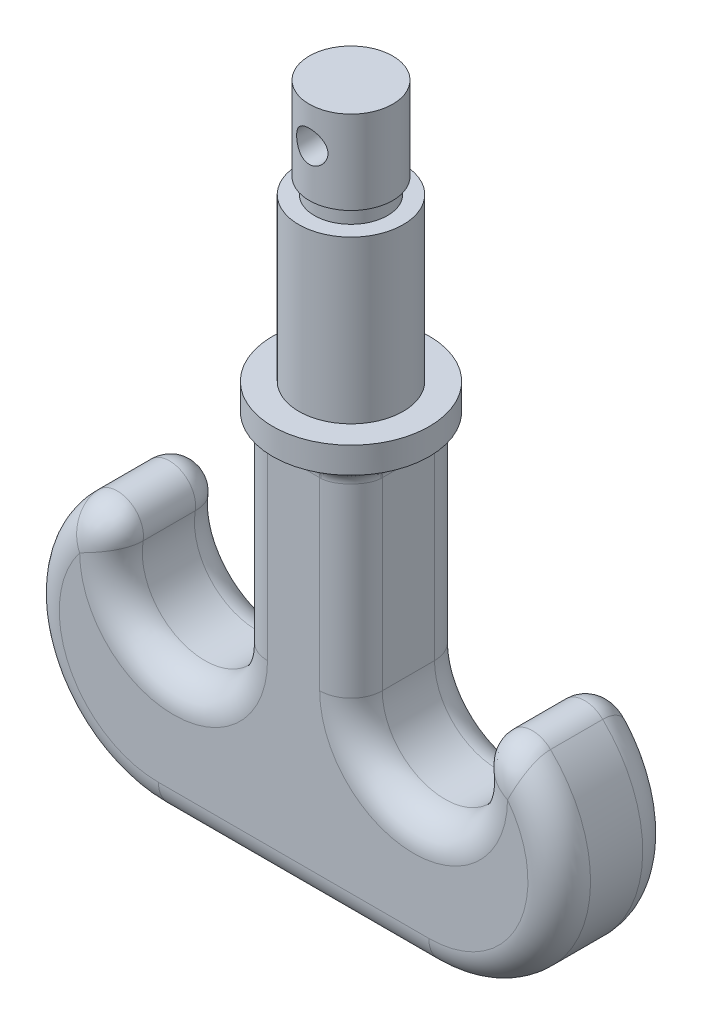
SolidWorks part; units mm, degrees
ref_plane "Front Plane" through (0, 0, 0) normal (0, 0, 1) x (1, 0, 0)
ref_plane "Top Plane" through (0, 0, 0) normal (0, 1, 0) x (1, 0, 0)
ref_plane "Right Plane" through (0, 0, 0) normal (1, 0, 0) x (0, 0, -1)
sketch "Sketch1" plane through (0, 0, 0) normal (0, 0, 1) x (1, 0, 0)
  line L0 (0, 125.5092) -> (0, 0) construction
  line L1 (0, 0) -> (0, 75)
  line L2 (11, 75) -> (-11, 75)
  line L3 (-11, 75) -> (-11, 36.6426)
  line L4 (-25.907, 0) -> (25.907, 0)
  line L5 (11, 75) -> (11, 36.6426)
  arc A0 (-11, 36.6426) -> (-34.8396, 38.5983) centre (-23, 36.6426) cw
  arc A1 (-34.8396, 38.5983) -> (-43.2391, 43.0165) centre (-39.7727, 39.4132) ccw
  arc A2 (-43.2391, 43.0165) -> (-25.907, 0) centre (-25.907, 25) ccw
  arc A3 (43.2391, 43.0165) -> (25.907, 0) centre (25.907, 25) cw
  arc A4 (34.8396, 38.5983) -> (43.2391, 43.0165) centre (39.7727, 39.4132) cw
  arc A5 (11, 36.6426) -> (34.8396, 38.5983) centre (23, 36.6426) ccw
  point P22 (49.0955, 15.6569)
  dimension "D1" = 75
  dimension "D3" = 12
  dimension "D4" = 5
  dimension "D5" = 25
  dimension "D2" = 11
extrude "Boss-Extrude2" add sketch "Sketch1" along normal mid plane 22 contours A1 A2 L4 L1 L2 L3 A0 | A5 L5 L2 L1 L4 A3 A4 region at (-12.9535, 0.9065, 0) region at (0.9065, 37.5, 0)
ref_plane "Plane1" through (0, 0, 0) normal (0, 0, 1) x (1, 0, 0)
sketch "Sketch4" plane through (0, 0, 0) normal (0, 0, 1) x (1, 0, 0)
  line L0 (0, 0) -> (0, 168.7307) construction
  line L1 (-25.907, 0) -> (25.907, 0) construction
  line L2 (0, 75) -> (15, 75)
  line L3 (11, 75) -> (-11, 75) construction
  line L4 (15, 75) -> (15, 80)
  line L5 (15, 80) -> (10, 80)
  line L6 (10, 80) -> (10, 111)
  line L7 (10, 111) -> (7, 111)
  line L8 (7, 111) -> (7, 114)
  line L9 (7, 114) -> (8, 114)
  line L10 (8, 114) -> (8, 130)
  line L11 (8, 130) -> (0, 130)
  line L12 (0, 75) -> (0, 130)
  dimension "D1" = 15
  dimension "D2" = 5
  dimension "D3" = 10
  dimension "D4" = 7
  dimension "D5" = 8
  dimension "D6" = 31
  dimension "D7" = 3
  dimension "D8" = 16
revolve "Revolve1" add sketch "Sketch4" angle 360 about L0
cosmetic thread "Cosmetic Thread1" parameters "D2"=13.797
sketch "Sketch5" plane through (0, 0, 0) normal (0, 0, 1) x (1, 0, 0)
  line L0 (8, 130) -> (-8, 130) construction
  circle A0 centre (0, 123) radius 3
  dimension "D1" = 6
  dimension "D2" = 7
extrude "Cut-Extrude1" cut sketch "Sketch5" against normal through all and the other way through all
fillet "Fillet1" radius 6 18 edges at (-11, 55.8213, -11) (-23.9812, 24.6828, -11) (-37.4451, 43.8384, -11) (-49.0955, 15.6569, -11) (0, 0, -11) (49.0955, 15.6569, -11) (37.4451, 43.8384, -11) (23.9812, 24.6828, -11) (-11, 55.8213, 11) (11, 55.8213, 11) (23.9812, 24.6828, 11) (37.4451, 43.8384, 11) (49.0955, 15.6569, 11) (0, 0, 11) (-49.0955, 15.6569, 11) (-37.4451, 43.8384, 11) (11, 55.8213, -11) (-23.9812, 24.6828, 11)
fillet "Fillet2" radius 3 8 edges at (9.2426, 75, 9.2426) (11, 75, 0) (9.2426, 75, -9.2426) (0, 75, -11) (-9.2426, 75, -9.2426) (-11, 75, 0) (-9.2426, 75, 9.2426) (0, 75, 11)
